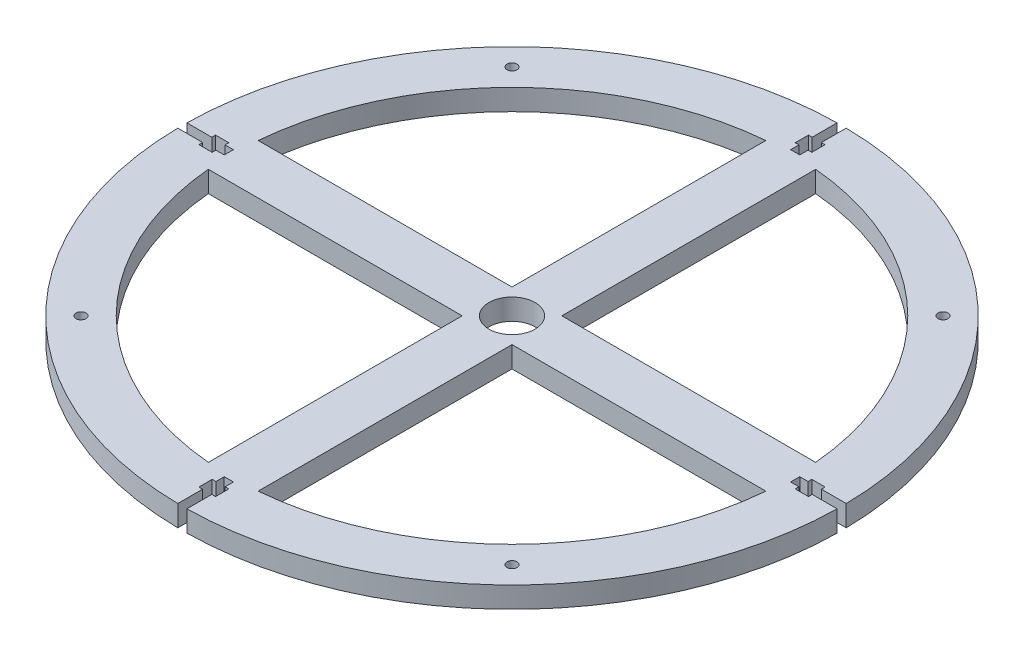
SolidWorks part; units mm, degrees
material "6061 Alloy"
ref_plane "Front Plane" through (0, 0, 0) normal (0, 0, 1) x (1, 0, 0)
ref_plane "Top Plane" through (0, 0, 0) normal (0, 1, 0) x (1, 0, 0)
ref_plane "Right Plane" through (0, 0, 0) normal (1, 0, 0) x (0, 0, -1)
sketch "Sketch1" plane through (0, 0, 0) normal (0, 1, 0) x (1, 0, 0)
  line L0 (0, -99.238) -> (0, 99.238) construction
  line L1 (-99.238, 0) -> (99.238, 0) construction
  line L2 (-98.9542, -7.5) -> (98.9542, -7.5)
  line L3 (7.5, -98.9542) -> (7.5, 98.9542)
  line L4 (-98.9542, 7.5) -> (98.9542, 7.5)
  line L5 (-7.5, -98.9542) -> (-7.5, 98.9542)
  line L6 (-7.5, -99.238) -> (-7.5, 99.238) construction
  line L7 (7.5, -99.238) -> (7.5, 99.238) construction
  line L8 (-99.238, -7.5) -> (99.238, -7.5) construction
  line L9 (-99.238, 7.5) -> (99.238, 7.5) construction
  circle A0 centre (0, 0) radius 100 construction
  circle A1 centre (0, 0) radius 99.238
  circle A2 centre (0, 0) radius 84.238
  point P7 (0, 0)
  point P11 (0, 0)
  dimension "D1" = 200
  dimension "D2" = 0.762
  dimension "D3" = 15
  dimension "D4" = 7.5
  dimension "D5" = 7.5
extrude "Boss-Extrude1" add sketch "Sketch1" along normal mid plane 6.35 contours A2 L2 A1 L5 | A2 L4 A1 L2 | A2 L5 A1 L4 | A2 L3 A1 L5 | A2 L4 A1 L3 | A2 L2 A1 L4 | A2 L3 A1 L2 | A2 L5 A1 L3 | L5 A2 L3 L2 | L4 A2 L2 L5 | L3 A2 L5 L4 | L2 A2 L4 L3 | L5 L2 L3 L4 region at (-91.6349, 0, 0) region at (-59.7933, 0, 59.7933) region at (-45.8134, 0, 0) region at (-59.7933, 0, -59.7933) region at (0, 0, 91.6349) region at (0, 0, 0) region at (0, 0, 45.8134) region at (0, 0, -91.6349) region at (59.7933, 0, 59.7933) region at (45.8134, 0, 0) region at (0, 0, -45.8134) region at (59.7933, 0, -59.7933) region at (91.6349, 0, 0)
sketch "Sketch2" plane through (0, 0, 0) normal (0, 1, 0) x (1, 0, 0)
  line L0 (-1.375, 85.238) -> (-1.375, 99.238)
  line L1 (-1.375, 85.238) -> (1.375, 85.238)
  line L2 (-1.375, 99.238) -> (1.375, 99.238)
  line L3 (1.375, 85.238) -> (1.375, 99.238)
  line L4 (-1.375, 85.238) -> (1.375, 99.238) construction
  line L5 (-1.375, 99.238) -> (1.375, 85.238) construction
  line L6 (-2.5, 87.738) -> (-2.5, 91.738)
  line L7 (-2.5, 87.738) -> (2.5, 87.738)
  line L8 (-2.5, 91.738) -> (2.5, 91.738)
  line L9 (2.5, 87.738) -> (2.5, 91.738)
  line L10 (-2.5, 87.738) -> (2.5, 91.738) construction
  line L11 (-2.5, 91.738) -> (2.5, 87.738) construction
  line L12 (0, -1000) -> (0, 49000) construction
  line L13 (-1000, 0) -> (49000, 0) construction
  circle A0 centre (0, 0) radius 99.238 construction
  point P1 (0, 92.238)
  point P2 (0, 89.738)
  dimension "D1" = 2.75
  dimension "D2" = 14
  dimension "D3" = 4
  dimension "D4" = 5
  dimension "D5" = 2.5
extrude "Cut-Extrude1" cut sketch "Sketch2" against normal through all both and the other way through all contours L7 L0 L1 L3 | L8 L0 L7 L3 | L7 L9 L8 L3 | L0 L8 L3 L2 | L8 L6 L7 L0 region at (0, 0, -86.488) region at (-1.9375, 0, -89.738) region at (0, 0, -89.738) region at (0, 0, -95.488) region at (1.9375, 0, -89.738)
pattern_circular "CirPattern1" count 4 over 360 about axis through (0, 3.175, 0) along (0, 1, 0) of "Cut-Extrude1"
hole_wizard "Ø3.0 (3) Diameter Hole1" positions "Sketch3" profile "Sketch4" hole size "Ø3.0" standard "ANSI Metric" end condition up to next
sketch "Sketch3" plane through (0, 3.175, 0) normal (0, 1, 0) x (1, 0, 0)
  line L0 (-70.1719, -70.1719) -> (70.1719, 70.1719) construction
  line L2 (-70.1719, 70.1719) -> (70.1719, -70.1719) construction
  line L4 (70.1719, 70.1719) -> (59.5653, 59.5653)
  line L6 (70.1719, -70.1719) -> (59.5653, -59.5653)
  line L8 (-70.1719, -70.1719) -> (-59.5653, -59.5653)
  line L10 (-70.1719, 70.1719) -> (-59.5653, 59.5653)
  arc A0 (99.2285, 1.375) -> (1.375, 99.2285) centre (0, 0) ccw construction
  arc A1 (1.375, -99.2285) -> (99.2285, -1.375) centre (0, 0) ccw construction
  arc A2 (83.9035, 7.5) -> (7.5, 83.9035) centre (0, 0) ccw construction
  arc A3 (7.5, -83.9035) -> (83.9035, -7.5) centre (0, 0) ccw construction
  arc A4 (-83.9035, -7.5) -> (-7.5, -83.9035) centre (0, 0) ccw construction
  arc A5 (-7.5, 83.9035) -> (-83.9035, 7.5) centre (0, 0) ccw construction
  point P107 (0, 0)
  point P324 (0, 0)
  point P360 (-64.8686, 64.8686)
  point P362 (64.8686, 64.8686)
  point P364 (64.8686, -64.8686)
  point P366 (-64.8686, -64.8686)
sketch "Sketch4" plane through (-64.8686, 3.175, 64.8686) normal (1, 0, 0) x (0, 0, 1)
  line L0 (0, 0) -> (0, 6.35)
  line L1 (0, 6.35) -> (1.5, 6.35)
  line L2 (1.5, 6.35) -> (1.5, 0)
  line L5 (1.5, 0) -> (0, 0)
  line L11 (0, -6.35) -> (0, 107.95) construction
  dimension "Thru Hole Dia." = 3
  dimension "Thru Hole Depth" = 6.35
hole_wizard "1/2 Clearance Hole1" positions "Sketch5" profile "Sketch6" hole size "1/2" standard "ANSI Inch" end condition up to next
sketch "Sketch5" plane through (0, 3.175, 0) normal (0, 1, 0) x (1, 0, 0)
  point P0 (0, 0)
sketch "Sketch6" plane through (0, 3.175, 0) normal (1, 0, 0) x (0, 0, 1)
  line L0 (0, 0) -> (0, 6.35)
  line L1 (0, 6.35) -> (6.9456, 6.35)
  line L2 (6.9456, 6.35) -> (6.9456, 0)
  line L5 (6.9456, 0) -> (0, 0)
  line L11 (0, -6.35) -> (0, 107.95) construction
  dimension "Thru Hole Dia." = 13.8913
  dimension "Thru Hole Depth" = 6.35
